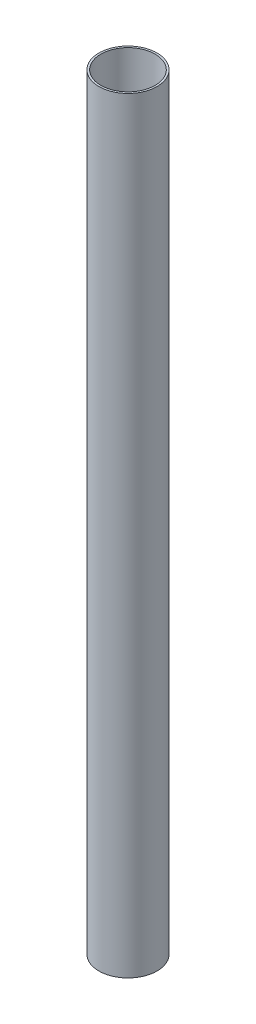
SolidWorks part; units mm, degrees
material "E-Glass Fiber"
ref_plane "Front Plane" through (0, 0, 0) normal (0, 0, 1) x (1, 0, 0)
ref_plane "Top Plane" through (0, 0, 0) normal (0, 1, 0) x (1, 0, 0)
ref_plane "Right Plane" through (0, 0, 0) normal (1, 0, 0) x (0, 0, -1)
sketch "Sketch1" plane through (0, 0, 0) normal (0, 0, 1) x (1, 0, 0)
  line L0 (0, 0) -> (0, -40.98) construction
  line L1 (28.9179, 27.6862) -> (28.9179, -734.3138) construction
  line L2 (26.9875, 27.6862) -> (28.9179, 27.6862)
  line L3 (26.9875, 27.6862) -> (26.9875, -734.3138)
  line L4 (26.9875, -734.3138) -> (28.9179, -734.3138)
  line L5 (28.9179, 27.6862) -> (28.9179, -734.3138)
revolve "Revolve1" add sketch "Sketch1" angle 360 about L0
